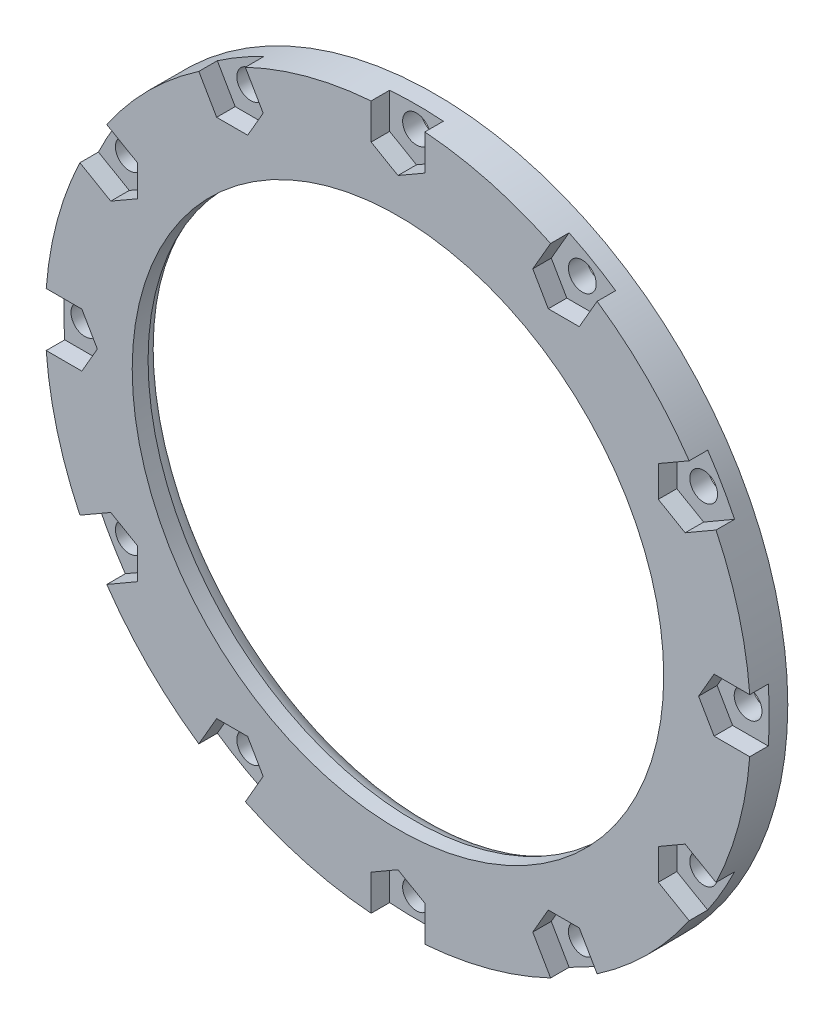
SolidWorks part; units mm, degrees
ref_plane "Front Plane" through (0, 0, 0) normal (0, 0, 1) x (1, 0, 0)
ref_plane "Top Plane" through (0, 0, 0) normal (0, 1, 0) x (1, 0, 0)
ref_plane "Right Plane" through (0, 0, 0) normal (1, 0, 0) x (0, 0, -1)
sketch "Sketch1" plane through (0, 0, 0) normal (0, 0, 1) x (1, 0, 0)
  circle A0 centre (0, 0) radius 38.1
  circle A1 centre (0, 0) radius 28.702
  dimension "D1" = 76.2
  dimension "D2" = 57.404
extrude "Boss-Extrude1" add sketch "Sketch1" along normal blind 4
sketch "Sketch2" plane through (0, 0, 4) normal (0, 0, 1) x (1, 0, 0)
  line L0 (0, 0) -> (0, 44.3901) construction
  circle A0 centre (0, 0) radius 35.814 construction
  circle A1 centre (0, 35.814) radius 1.5
  circle A2 centre (17.907, 31.0158) radius 1.5
  circle A3 centre (31.0158, 17.907) radius 1.5
  circle A4 centre (35.814, 0) radius 1.5
  circle A5 centre (31.0158, -17.907) radius 1.5
  circle A6 centre (17.907, -31.0158) radius 1.5
  circle A7 centre (0, -35.814) radius 1.5
  circle A8 centre (-17.907, -31.0158) radius 1.5
  circle A9 centre (-31.0158, -17.907) radius 1.5
  circle A10 centre (-35.814, 0) radius 1.5
  circle A11 centre (-31.0158, 17.907) radius 1.5
  circle A12 centre (-17.907, 31.0158) radius 1.5
  point P30 (0, 0)
  dimension "D1" = 71.628
  dimension "D2" = 3
  dimension "D3" = 12
extrude "Cut-Extrude1" cut sketch "Sketch2" against normal through all
sketch "Sketch3" plane through (0, 0, 4) normal (0, 0, 1) x (1, 0, 0)
  line L0 (0, 0) -> (0, 45.6158) construction
  line L1 (-2.9, 37.9895) -> (0, 39.1626)
  line L2 (16.4833, 34.3498) -> (19.5813, 33.9158)
  line L3 (-2.9, 37.9895) -> (-2.9, 34.1397)
  line L4 (-2.9, 34.1397) -> (0, 32.4654)
  line L5 (0, 32.4654) -> (2.9, 34.1397)
  line L6 (2.9, 34.1397) -> (2.9, 37.9895)
  line L7 (16.4833, 34.3498) -> (14.5584, 31.0158)
  line L8 (0, 39.1626) -> (2.9, 37.9895)
  line L9 (14.5584, 31.0158) -> (16.2327, 28.1158)
  line L10 (16.2327, 28.1158) -> (19.5813, 28.1158)
  line L11 (19.5813, 28.1158) -> (21.5062, 31.4498)
  line L12 (19.5813, 33.9158) -> (21.5062, 31.4498)
  line L13 (31.4498, 21.5062) -> (33.9158, 19.5813)
  line L14 (31.4498, 21.5062) -> (28.1158, 19.5813)
  line L15 (28.1158, 19.5813) -> (28.1158, 16.2327)
  line L16 (28.1158, 16.2327) -> (31.0158, 14.5584)
  line L17 (31.0158, 14.5584) -> (34.3498, 16.4833)
  line L18 (33.9158, 19.5813) -> (34.3498, 16.4833)
  line L19 (37.9895, 2.9) -> (39.1626, 0)
  line L20 (37.9895, 2.9) -> (34.1397, 2.9)
  line L21 (34.1397, 2.9) -> (32.4654, 0)
  line L22 (32.4654, 0) -> (34.1397, -2.9)
  line L23 (34.1397, -2.9) -> (37.9895, -2.9)
  line L24 (39.1626, 0) -> (37.9895, -2.9)
  line L25 (34.3498, -16.4833) -> (33.9158, -19.5813)
  line L26 (34.3498, -16.4833) -> (31.0158, -14.5584)
  line L27 (31.0158, -14.5584) -> (28.1158, -16.2327)
  line L28 (28.1158, -16.2327) -> (28.1158, -19.5813)
  line L29 (28.1158, -19.5813) -> (31.4498, -21.5062)
  line L30 (33.9158, -19.5813) -> (31.4498, -21.5062)
  line L31 (21.5062, -31.4498) -> (19.5813, -33.9158)
  line L32 (21.5062, -31.4498) -> (19.5813, -28.1158)
  line L33 (19.5813, -28.1158) -> (16.2327, -28.1158)
  line L34 (16.2327, -28.1158) -> (14.5584, -31.0158)
  line L35 (14.5584, -31.0158) -> (16.4833, -34.3498)
  line L36 (19.5813, -33.9158) -> (16.4833, -34.3498)
  line L37 (2.9, -37.9895) -> (0, -39.1626)
  line L38 (2.9, -37.9895) -> (2.9, -34.1397)
  line L39 (2.9, -34.1397) -> (0, -32.4654)
  line L40 (0, -32.4654) -> (-2.9, -34.1397)
  line L41 (-2.9, -34.1397) -> (-2.9, -37.9895)
  line L42 (0, -39.1626) -> (-2.9, -37.9895)
  line L43 (-16.4833, -34.3498) -> (-19.5813, -33.9158)
  line L44 (-16.4833, -34.3498) -> (-14.5584, -31.0158)
  line L45 (-14.5584, -31.0158) -> (-16.2327, -28.1158)
  line L46 (-16.2327, -28.1158) -> (-19.5813, -28.1158)
  line L47 (-19.5813, -28.1158) -> (-21.5062, -31.4498)
  line L48 (-19.5813, -33.9158) -> (-21.5062, -31.4498)
  line L49 (-31.4498, -21.5062) -> (-33.9158, -19.5813)
  line L50 (-31.4498, -21.5062) -> (-28.1158, -19.5813)
  line L51 (-28.1158, -19.5813) -> (-28.1158, -16.2327)
  line L52 (-28.1158, -16.2327) -> (-31.0158, -14.5584)
  line L53 (-31.0158, -14.5584) -> (-34.3498, -16.4833)
  line L54 (-33.9158, -19.5813) -> (-34.3498, -16.4833)
  line L55 (-37.9895, -2.9) -> (-39.1626, 0)
  line L56 (-37.9895, -2.9) -> (-34.1397, -2.9)
  line L57 (-34.1397, -2.9) -> (-32.4654, 0)
  line L58 (-32.4654, 0) -> (-34.1397, 2.9)
  line L59 (-34.1397, 2.9) -> (-37.9895, 2.9)
  line L60 (-39.1626, 0) -> (-37.9895, 2.9)
  line L61 (-34.3498, 16.4833) -> (-33.9158, 19.5813)
  line L62 (-34.3498, 16.4833) -> (-31.0158, 14.5584)
  line L63 (-31.0158, 14.5584) -> (-28.1158, 16.2327)
  line L64 (-28.1158, 16.2327) -> (-28.1158, 19.5813)
  line L65 (-28.1158, 19.5813) -> (-31.4498, 21.5062)
  line L66 (-33.9158, 19.5813) -> (-31.4498, 21.5062)
  line L67 (-21.5062, 31.4498) -> (-19.5813, 33.9158)
  line L68 (-21.5062, 31.4498) -> (-19.5813, 28.1158)
  line L69 (-19.5813, 28.1158) -> (-16.2327, 28.1158)
  line L70 (-16.2327, 28.1158) -> (-14.5584, 31.0158)
  line L71 (-14.5584, 31.0158) -> (-16.4833, 34.3498)
  line L72 (-19.5813, 33.9158) -> (-16.4833, 34.3498)
  line L139 (-1.45, 38.3255) -> (-1.9248, 38.0513) [skipped]
  line L140 (1.9248, 38.0513) -> (1.45, 38.3255) [skipped]
  circle A0 centre (0, 35.814) radius 2.9 construction
  circle A1 centre (0, 0) radius 38.1 construction
  circle A2 centre (17.907, 31.0158) radius 2.9 construction
  circle A3 centre (31.0158, 17.907) radius 2.9 construction
  circle A4 centre (35.814, 0) radius 2.9 construction
  circle A5 centre (31.0158, -17.907) radius 2.9 construction
  circle A6 centre (17.907, -31.0158) radius 2.9 construction
  circle A7 centre (0, -35.814) radius 2.9 construction
  circle A8 centre (-17.907, -31.0158) radius 2.9 construction
  circle A9 centre (-31.0158, -17.907) radius 2.9 construction
  circle A10 centre (-35.814, 0) radius 2.9 construction
  circle A11 centre (-31.0158, 17.907) radius 2.9 construction
  circle A12 centre (-17.907, 31.0158) radius 2.9 construction
  point P103 (0, 0)
  point P104 (0, 0)
  dimension "D1" = 5.8
  dimension "D2" = 12
extrude "Cut-Extrude2" cut sketch "Sketch3" against normal blind 2
sketch "Sketch4" plane through (0, 0, 0) normal (0, 1, 0) x (1, 0, 0)
  line L0 (0, -24.7946) -> (0, 28.58) construction
  line L1 (31.75, 0) -> (0, 0)
  line L2 (0, 0) -> (0, -3.175)
  line L3 (38.1, 0) -> (-38.1, 0) construction
  line L6 (28.575, -3.175) -> (0, -3.175)
  arc A0 (31.75, 0) -> (28.575, -3.175) centre (31.75, -3.175) ccw
  dimension "D2" = 3.175
  dimension "D1" = 28.575
  dimension "D3" = 3.175
revolve "Cut-Revolve1" cut sketch "Sketch4" angle 360 about L0
